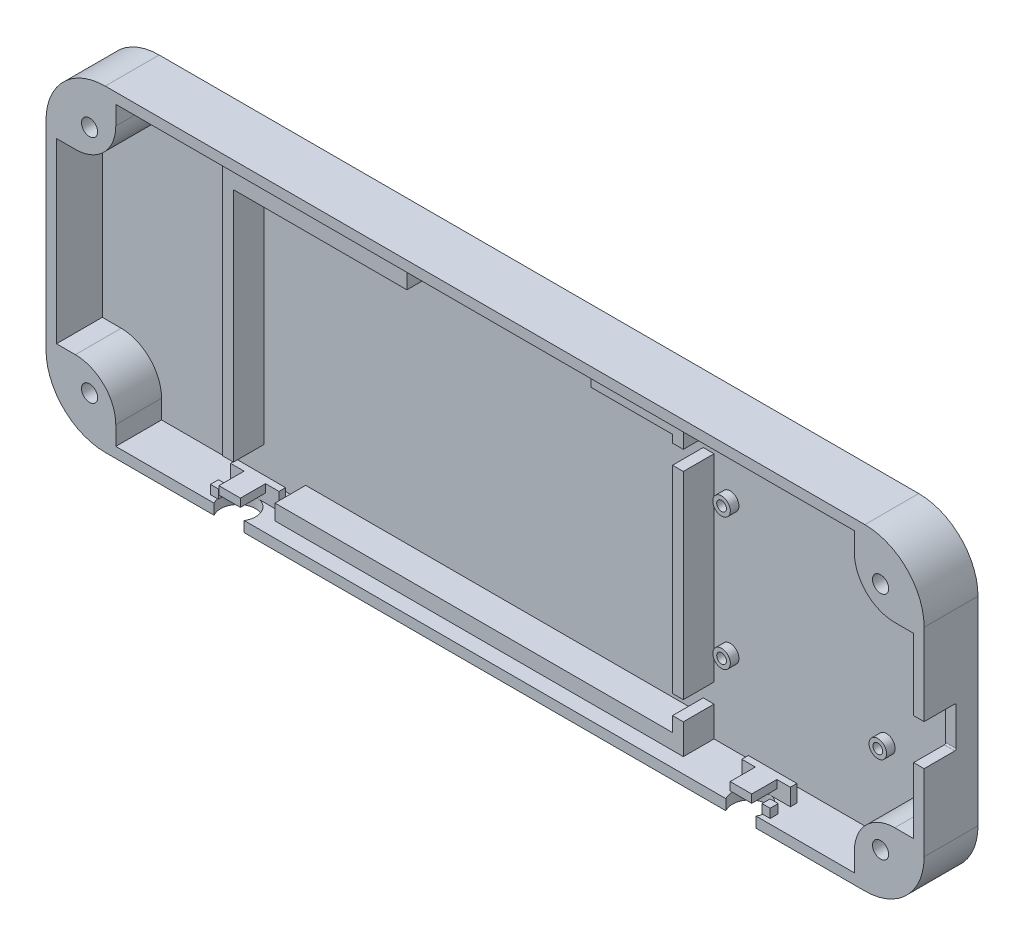
SolidWorks part; units mm, degrees
note: The reader was unsure of these and kept them because the rebuilt part matched: shared geometry of "Sketch1<3>", "Sketch6<2>", "Sketch11<3>", "Sketch12<3>".
ref_plane "Front Plane" through (0, 0, 0) normal (0, 0, 1) x (1, 0, 0)
ref_plane "Top Plane" through (0, 0, 0) normal (0, 1, 0) x (1, 0, 0)
ref_plane "Right Plane" through (0, 0, 0) normal (1, 0, 0) x (0, 0, -1)
sketch "Sketch1" plane through (0, 0, 0) normal (0, 0, 1) x (1, 0, 0)
  line L0 (0, 55) -> (0, 58.9) construction
  line L1 (163, 58.9) -> (-163, 58.9)
  line L2 (163, 58.9) -> (163, -58.9)
  line L3 (163, -58.9) -> (-163, -58.9)
  line L4 (-163, 58.9) -> (-163, -58.9)
  line L5 (163, 58.9) -> (-163, -58.9) construction
  line L6 (163, -58.9) -> (-163, 58.9) construction
  line L7 (-159.1, -55) -> (159.1, -55)
  line L8 (-159.1, -55) -> (-159.1, 55)
  line L9 (-159.1, 55) -> (159.1, 55)
  line L10 (159.1, -55) -> (159.1, 55)
  line L11 (-159.1, -55) -> (159.1, 55) construction
  line L12 (-159.1, 55) -> (159.1, -55) construction
  line L13 (-159.1, 0) -> (-163, 0) construction
  line L14 (159.1, 4.25) -> (159.1, -6.25) construction
  point P0 (0, 0)
  point P6 (0, 0)
  dimension "D1" = 3.9
  dimension "D2" = 110
extrude "Boss-Extrude1" add sketch "Sketch1" along normal blind 20 contours L1 L4 L3 L2 L10 L7 L8 L9
extrude "Boss-Extrude2" add sketch "Sketch1<3>" along normal blind 3 contours L7 L10 L9 L8
sketch "Sketch1<3>" plane through (0, 0, 0) normal (0, 0, 1) x (1, 0, 0) same geometry as "Sketch1"
sketch "Sketch5" plane through (0, 0, 0) normal (0, 0, 1) x (1, 0, 0)
  line L0 (64, 55) -> (64, 43.7953)
  line L1 (-159.1, 55) -> (159.1, 55) construction
  line L2 (-159.1, -55) -> (159.1, -55) construction
  line L3 (64, -55) -> (68, -55)
  line L4 (68, -55) -> (68, -43.7953)
  line L5 (68, 55) -> (64, 55)
  line L6 (68, -36.6942) -> (64, -36.6942)
  line L7 (-99, -43.7953) -> (-103, -43.7953)
  line L8 (-103, -43.7953) -> (-103, 55)
  line L9 (-103, 55) -> (-99, 55)
  line L10 (-99, 55) -> (-99, -43.7953)
  line L12 (64, -49.2598) -> (-83.5893, -49.2598)
  line L13 (68, 43.7953) -> (68, 55)
  line L14 (64, -43.7953) -> (68, -43.7953)
  line L15 (64, 36.6942) -> (68, 36.6942)
  line L16 (64, 43.7953) -> (68, 43.7953)
  line L17 (68, -36.6942) -> (68, 36.6942)
  line L18 (64, -43.7953) -> (64, -55)
  line L19 (64, 36.6942) -> (64, -36.6942)
  line L20 (0, 0) -> (61.1826, 0) construction
  line L21 (163, 58.9) -> (163, -58.9) construction
  line L22 (-83.5893, -49.2598) -> (-83.5893, -55)
  line L23 (-137.1, -55) -> (-67.7766, -55) construction
  line L24 (-83.5893, -55) -> (64, -55)
  line L25 (-99, 43.7953) -> (-34.5955, 43.7953)
  line L26 (-34.5955, 43.7953) -> (-34.5955, 55)
  line L27 (-137.1, 55) -> (-24, 55) construction
  line L28 (-34.5955, 55) -> (-99, 55)
  line L29 (64, 46.6245) -> (33.7813, 46.6245)
  line L31 (33.7813, 46.6245) -> (33.7813, 55)
  line L32 (24, 55) -> (137.1, 55) construction
  line L33 (33.7813, 55) -> (64, 55)
  dimension "D1" = 4
  dimension "D2" = 163
  dimension "D3" = 99
sketch "Sketch6" plane through (0, 0, 0) normal (0, 0, 1) x (1, 0, 0)
  line L1 (-163, 0) -> (159.1, 0) construction
  line L2 (-163, 58.9) -> (-163, -58.9) construction
  line L3 (159.1, -55) -> (159.1, 55) construction
  circle A11 centre (132, -24.5) radius 1.8
  circle A12 centre (132, -24.5) radius 3.25
  circle A13 centre (74, -24.5) radius 1.8
  circle A14 centre (74, -24.5) radius 3.25
  circle A15 centre (74, 24.5) radius 1.8
  circle A17 centre (74, 24.5) radius 3.25
  circle A18 centre (132, 24.5) radius 1.8
  circle A19 centre (132, 24.5) radius 3.25
  dimension "D1" = 3.6
  dimension "D2" = 6.5
extrude "Boss-Extrude6" add sketch "Sketch6" along normal blind 3.2 from surface at 3 starting at face at (0, 0, 3)
fillet "Fillet1" radius 22 8 edges at (163, -58.9, 10) (163, 58.9, 10) (-163, -58.9, 10) (-163, 58.9, 10) (159.1, -55, 11.5) (159.1, 55, 11.5) (-159.1, -55, 11.5) (-159.1, 55, 11.5)
sketch "Sketch9" plane through (0, 0, 0) normal (1, 0, 0) x (0, 0, -1)
  line L0 (-20, -8.55) -> (-8.58, -8.55)
  line L2 (-20, -33) -> (-20, 33) construction
  line L3 (-8.08, -8.05) -> (-8.08, 6.05)
  line L4 (-8.58, 6.55) -> (-20, 6.55)
  line L6 (-20, 6.55) -> (-20, -8.55)
  line L9 (-22.5, -3.9) -> (-22.5, 1.9) construction
  line L10 (-8.08, -1) -> (-22.5, -1) construction
  line L11 (-17.28, 5.25) -> (-18.44, 5.25) construction
  line L13 (-9.38, -6.55) -> (-9.38, -1.01) construction
  arc A0 (-8.08, 6.05) -> (-8.58, 6.55) centre (-8.58, 6.05) ccw
  arc A1 (-8.58, -8.55) -> (-8.08, -8.05) centre (-8.58, -8.05) ccw
  dimension "D2" = 0.5
  dimension "D1" = 1.3
  dimension "D3" = 1.3
extrude "Cut-Extrude3" cut sketch "Sketch9" against normal up to surface (3.9 mm away) from surface at 163 up to face at (159.1, 0, 11.5) starting at face at (163, 0, 10)
extrude "Cut-Extrude4" cut sketch "Sketch6<2>" against normal blind 1.8 from surface at 3 contours A11 | A18 | A15 | A13 starting at face at (135.25, 24.5, 3)
sketch "Sketch6<2>" plane through (0, 0, 0) normal (0, 0, 1) x (1, 0, 0) same geometry as "Sketch6"
extrude "Boss-Extrude7" add sketch "Sketch5" along normal blind 14.4
sketch "Sketch10" plane through (0, 0, 0) normal (0, 1, 0) x (1, 0, 0)
  line L0 (-163, -16.6656) -> (163, -16.6656) construction
  line L1 (0, 0) -> (0, -20) construction
  line L2 (141, -20) -> (-141, -20) construction
  line L3 (163, -20) -> (163, 0) construction
  line L4 (-163, 0) -> (-163, -20) construction
  line L5 (141, 0) -> (-141, 0) construction
  circle A0 centre (95, -16.6656) radius 6.5
  circle A1 centre (-95, -16.6656) radius 6.5
  dimension "D2" = 13
  dimension "D1" = 95
  dimension "D3" = 16.6656
extrude "Cut-Extrude5" cut sketch "Sketch10" against normal up to surface (3.9 mm away) from surface
sketch "Sketch11" plane through (0, 0, 0) normal (0, 1, 0) x (1, 0, 0)
  line L0 (91, -8.2356) -> (99, -8.2356)
  line L1 (99, -10.6656) -> (99, -20)
  line L2 (99, -20) -> (91, -20)
  line L3 (91, -20) -> (91, -10.6656)
  line L4 (95, -16.6656) -> (95, -8.2356) construction
  line L5 (104, -10.6656) -> (86, -10.6656)
  line L6 (86, -10.6656) -> (86, -8.2356)
  line L7 (86, -8.2356) -> (104, -8.2356)
  line L8 (104, -8.2356) -> (104, -10.6656)
  line L9 (-89.4204, -20) -> (89.4204, -20) construction
  line L10 (104, -15.1656) -> (101, -15.1656)
  line L11 (101, -11.6656) -> (101, -21.6656) construction
  line L12 (101, -15.1656) -> (101, -18.1656)
  line L13 (101, -18.1656) -> (104, -18.1656)
  line L14 (104, -18.1656) -> (104, -15.1656)
  line L15 (95, -16.6656) -> (104, -16.6656) construction
  line L17 (101.35, -19.1656) -> (102.05, -19.1656) construction
  line L18 (0, 0) -> (-0.0266, -23.6313) construction
  line L19 (-60.5266, -23.6313) -> (60.4734, -23.6313) construction
  line L20 (-86.0238, -10.4716) -> (-86.0184, -8.0417)
  line L21 (-99.0449, -19.7767) -> (-91.0449, -19.7947)
  line L22 (-91.0449, -19.7947) -> (-91.0238, -10.4604)
  line L23 (-101.0339, -14.9378) -> (-101.0407, -17.9378)
  line L24 (-101.0407, -17.9378) -> (-104.0407, -17.931)
  line L25 (-104.0407, -17.931) -> (-104.0339, -14.931)
  line L26 (-104.0339, -14.931) -> (-101.0339, -14.9378)
  line L27 (-99.0238, -10.4423) -> (-99.0449, -19.7767)
  line L28 (-86.0184, -8.0417) -> (-104.0183, -8.0011)
  line L29 (-104.0238, -10.431) -> (-86.0238, -10.4716)
  line L30 (-104.0183, -8.0011) -> (-104.0238, -10.431)
  dimension "D1" = 8
  dimension "D2" = 18
  dimension "D3" = 1
  dimension "D4" = 6
extrude "Boss-Extrude8" add sketch "Sketch11" along normal blind 3.3 from surface at -55 contours L26 L25 L24 L23 | L28 L30 L29 L20 | L5 L6 L7 L8 | L13 L14 L10 L12 starting at face at (-2.5982, -55, 11.7609)
extrude "Boss-Extrude9" add sketch "Sketch11<3>" along normal blind 3 from surface at -51.7 contours L29 L27 L21 L22 | L1 L5 L3 L2 | L8 L7 L0 L6 L5
sketch "Sketch11<3>" plane through (0, 0, 0) normal (0, 1, 0) x (1, 0, 0) same geometry as "Sketch11"
sketch "Sketch12" plane through (0, 0, 0) normal (0, 0, 1) x (1, 0, 0)
  line L0 (0, 0) -> (0, -50000) construction
  line L1 (-163, 0) -> (163.7106, 0) construction
  line L10 (-137.1, -55) -> (-137.1, -48)
  line L11 (-152.1, -33) -> (-159.1, -33)
  line L12 (-137.1, -33) -> (-156.5563, -52.4563) construction
  line L13 (-163, 36.9) -> (-163, -36.9) construction
  line L14 (-137.1, -33) -> (-137.1, -55)
  line L15 (-159.1, -33) -> (-137.1, -33)
  line L16 (-137.1, 33) -> (-156.5563, 52.4563) construction
  line L17 (-159.1, 33) -> (-152.1, 33)
  line L18 (-137.1, 48) -> (-137.1, 55)
  line L19 (-137.1, 33) -> (-159.1, 33)
  line L20 (-137.1, 55) -> (-137.1, 33)
  line L21 (137.1, 33) -> (156.5563, 52.4563) construction
  line L22 (137.1, -33) -> (156.5563, -52.4563) construction
  line L23 (163, 0) -> (-163.7106, 0) construction
  line L24 (137.1, 55) -> (137.1, 48)
  line L25 (152.1, 33) -> (159.1, 33)
  line L26 (137.1, 33) -> (137.1, 55)
  line L27 (159.1, 33) -> (137.1, 33)
  line L28 (159.1, -33) -> (152.1, -33)
  line L29 (137.1, -48) -> (137.1, -55)
  line L30 (137.1, -33) -> (159.1, -33)
  line L31 (137.1, -55) -> (137.1, -33)
  circle A0 centre (-146.8282, -42.7282) radius 3
  arc A2 (-137.1, -55) -> (-159.1, -33) centre (-137.1, -33) cw
  arc A3 (-163, -36.9) -> (-141, -58.9) centre (-141, -36.9) ccw construction
  arc A4 (-137.1, 55) -> (-159.1, 33) centre (-137.1, 33) ccw
  circle A5 centre (-146.8282, 42.7282) radius 3
  circle A6 centre (146.8282, 42.7282) radius 3
  arc A7 (137.1, 55) -> (159.1, 33) centre (137.1, 33) cw
  arc A8 (137.1, -55) -> (159.1, -33) centre (137.1, -33) ccw
  circle A9 centre (146.8282, -42.7282) radius 3
  arc A10 (152.1, 33) -> (137.1, 48) centre (152.1, 48) cw
  arc A11 (-137.1, 48) -> (-152.1, 33) centre (-152.1, 48) cw
  arc A12 (-137.1, -48) -> (-152.1, -33) centre (-152.1, -48) ccw
  arc A13 (137.1, -48) -> (152.1, -33) centre (152.1, -48) cw
  dimension "D1" = 6
  dimension "D2" = 15
extrude "Boss-Extrude10" add sketch "Sketch12" against normal up to surface (17 mm away) from surface contours L10 A12 L11 A2 A0 | A11 L18 A4 L17 A5 | A10 L25 A7 L24 A6 | A13 L29 A8 L28 A9
extrude "Cut-Extrude6" cut sketch "Sketch12<3>" along normal blind 6 from surface at 0 contours A6 | A9 | A0 | A5 starting at face at (0, 0, 0)
sketch "Sketch12<3>" plane through (0, 0, 0) normal (0, 0, 1) x (1, 0, 0) same geometry as "Sketch12"
sketch "Sketch13" plane through (0, 0, 0) normal (0, 0, 1) x (1, 0, 0)
  circle A0 centre (-146.8282, -42.7282) radius 4.5
  circle A1 centre (-146.8282, 42.7282) radius 4.5
  circle A2 centre (146.8282, 42.7282) radius 4.5
  circle A3 centre (146.8282, -42.7282) radius 4.5
  dimension "D1" = 9
extrude "Cut-Extrude7" cut sketch "Sketch13" along normal blind 4 from surface at 0 starting at face at (-143.8282, 42.7282, 0)
